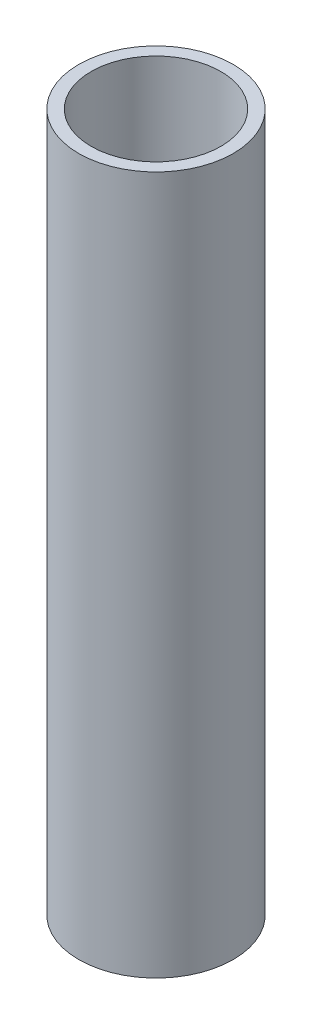
SolidWorks part; units mm, degrees
ref_plane "Front Plane" through (0, 0, 0) normal (0, 0, 1) x (1, 0, 0)
ref_plane "Top Plane" through (0, 0, 0) normal (0, 1, 0) x (1, 0, 0)
ref_plane "Right Plane" through (0, 0, 0) normal (1, 0, 0) x (0, 0, -1)
sketch "Sketch1" plane through (0, 0, 0) normal (0, 1, 0) x (1, 0, 0)
  circle A0 centre (0, 0) radius 12.5
  circle A1 centre (0, 0) radius 10.5
  dimension "D1" = 25
  dimension "D2" = 21
extrude "Boss-Extrude1" add sketch "Sketch1" along normal blind 113
equation "\"cf_tube_outer_diameter\" = 25mm"
equation "\"cf_tube_inner_diameter\" = 21mm"
equation "\"mid_plate_mid_to_top\" = 100mm"
equation "\"mid_plate_mid_to_bottom\" = 30mm"
equation "\"mid_plate_horizontal_spacing\" = 250mm"
equation "\"cf_plate_thickness\" = 4mm"
equation "\"mid_tube_length\" = 500mm"
equation "\"D1@Sketch1\"=\"cf_tube_outer_diameter\""
equation "\"D2@Sketch1\"=\"cf_tube_inner_diameter\""
